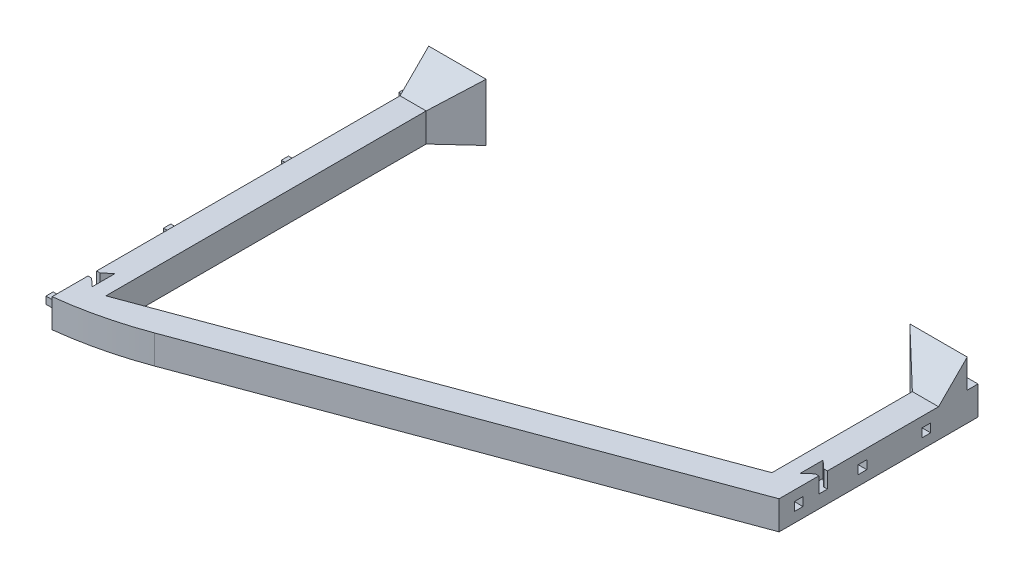
SolidWorks part; units mm, degrees
ref_plane "Přední rovina" through (0, 0, 0) normal (0, 0, 1) x (1, 0, 0)
ref_plane "Horní rovina" through (0, 0, 0) normal (0, 1, 0) x (1, 0, 0)
ref_plane "Pravá rovina" through (0, 0, 0) normal (1, 0, 0) x (0, 0, -1)
sketch "Skica1" plane through (0, 0, 0) normal (0, 1, 0) x (1, 0, 0)
  line L0 (0, 0) -> (0, -111)
  line L1 (0, -111) -> (150.15, -55.45)
  line L2 (150.15, -55.45) -> (150.15, 0)
  line L3 (150.15, 0) -> (142.85, 0)
  line L4 (142.85, 0) -> (142.85, -50.1539)
  line L5 (142.85, -50.1539) -> (7.3, -100.3024)
  line L6 (7.3, -100.3024) -> (7.3, 0)
  line L7 (7.3, 0) -> (0, 0)
  dimension "D1" = 7.3
  dimension "D2" = 7.3
  dimension "D3" = 111
  dimension "D4" = 7.5
  dimension "D5" = 150.15
  dimension "D6" = 55.45
extrude "Přidat vysunutím1" add sketch "Skica1" along normal blind 8
sketch "Skica2" plane through (0, 8, 0) normal (0, 1, 0) x (1, 0, 0)
  line L5 (0, -95.6) -> (1, -95.6)
  line L6 (0, 0) -> (0, -111) construction
  line L7 (1, -95.6) -> (3.2, -93.6)
  line L8 (3.2, -93.6) -> (3.2, -100)
  line L9 (3.2, -100) -> (1, -98)
  line L10 (1, -98) -> (0, -98)
  line L11 (0, -98) -> (0, -95.6)
  dimension "D1" = 6.4
  dimension "D2" = 2.4
  dimension "D3" = 1
  dimension "D4" = 1
  dimension "D5" = 2
  dimension "D6" = 3.2
  dimension "D7" = 11
extrude "Odebrat vysunutím1" cut sketch "Skica2" against normal blind 4.4
sketch "Skica3" plane through (0, 0, 0) normal (-1, 0, 0) x (0, 0, 1)
  line L0 (0, 8) -> (0, 0) construction
  line L1 (5.3, 5) -> (7.3, 5)
  line L2 (5.3, 5) -> (5.3, 3)
  line L3 (5.3, 3) -> (7.3, 3)
  line L4 (7.3, 5) -> (7.3, 3)
  line L5 (38.1, 5) -> (40.1, 5)
  line L6 (38.1, 5) -> (38.1, 3)
  line L7 (38.1, 3) -> (40.1, 3)
  line L8 (40.1, 5) -> (40.1, 3)
  line L9 (70.9, 5) -> (72.9, 5)
  line L10 (70.9, 5) -> (70.9, 3)
  line L11 (70.9, 3) -> (72.9, 3)
  line L12 (72.9, 5) -> (72.9, 3)
  line L17 (0, 8) -> (95.6, 8) construction
  line L18 (98, 8) -> (111, 8) construction
  line L19 (103.7, 5) -> (105.7, 5)
  line L20 (103.7, 5) -> (103.7, 3)
  line L21 (103.7, 3) -> (105.7, 3)
  line L22 (105.7, 5) -> (105.7, 3)
  point P16 (5.3, 4)
  dimension "D1" = 5.3
  dimension "D2" = 2
  dimension "D3" = 2
  dimension "D4" = 3
  dimension "D5" = 2
  dimension "D6" = 2
  dimension "D7" = 3
  dimension "D8" = 30.8
  dimension "D9" = 2
  dimension "D10" = 2
  dimension "D11" = 3
  dimension "D12" = 30.8
  dimension "D13" = 2
  dimension "D14" = 2
  dimension "D15" = 3
  dimension "D16" = 30.8
extrude "Přidat vysunutím2" add sketch "Skica3" along normal blind 4
sketch "Skica5" plane through (0, 8, 0) normal (0, 1, 0) x (1, 0, 0)
  line L0 (0, 0) -> (0, -95.6) construction
  line L1 (0, -3) -> (16, -3)
  line L2 (0, -3) -> (0, -11)
  line L3 (0, -11) -> (16, -11)
  line L4 (16, -3) -> (16, -11)
  line L5 (150.15, -55.45) -> (150.15, 0) construction
  line L6 (150.15, -3) -> (134.15, -3)
  line L7 (150.15, -3) -> (150.15, -11)
  line L8 (150.15, -11) -> (134.15, -11)
  line L9 (134.15, -3) -> (134.15, -11)
  line L10 (150.15, 0) -> (142.85, 0) construction
  line L11 (7.3, 0) -> (0, 0) construction
  dimension "D1" = 8
  dimension "D2" = 8
  dimension "D3" = 16
  dimension "D4" = 16
  dimension "D5" = 3
  dimension "D6" = 3
extrude "Přidat vysunutím3" add sketch "Skica5" against normal blind 16 from offset 8
sketch "Skica6" plane through (150.15, 0, 0) normal (1, 0, 0) x (0, 0, -1)
  line L0 (-11, 8) -> (-11, 16)
  line L1 (-11, 16) -> (-3, 16)
  line L2 (-3, 16) -> (-11, 8)
extrude "Odebrat vysunutím3" cut sketch "Skica6" against normal through all
sketch "Skica7" plane through (0, 0, 0) normal (0, -1, 0) x (1, 0, 0)
  line L0 (7.3, 11) -> (16, 3)
  line L1 (16, 3) -> (16, 11)
  line L2 (16, 11) -> (7.3, 11)
  line L3 (134.15, 3) -> (134.15, 11)
  line L4 (134.15, 11) -> (142.85, 11)
  line L5 (142.85, 11) -> (134.15, 3)
extrude "Odebrat vysunutím4" cut sketch "Skica7" against normal through all
sketch "Skica4" plane through (150.15, 0, 0) normal (1, 0, 0) x (0, 0, -1)
  line L0 (-55.45, 8) -> (-11, 8) construction
  line L1 (-51.2, 5.2) -> (-48.8, 5.2)
  line L2 (-51.2, 5.2) -> (-51.2, 2.8)
  line L3 (-51.2, 2.8) -> (-48.8, 2.8)
  line L4 (-48.8, 5.2) -> (-48.8, 2.8)
  line L5 (-33.4, 5.2) -> (-31, 5.2)
  line L6 (-33.4, 5.2) -> (-33.4, 2.8)
  line L7 (-33.4, 2.8) -> (-31, 2.8)
  line L8 (-31, 5.2) -> (-31, 2.8)
  line L9 (-15.6, 5.2) -> (-13.2, 5.2)
  line L10 (-15.6, 5.2) -> (-15.6, 2.8)
  line L11 (-15.6, 2.8) -> (-13.2, 2.8)
  line L12 (-13.2, 5.2) -> (-13.2, 2.8)
  line L14 (0, 8) -> (0, 0) construction
  point P16 (-31, 4)
  dimension "D1" = 2.4
  dimension "D2" = 2.4
  dimension "D3" = 2.8
  dimension "D4" = 2.4
  dimension "D5" = 2.4
  dimension "D6" = 2.8
  dimension "D7" = 2.4
  dimension "D8" = 2.4
  dimension "D9" = 2.8
  dimension "D10" = 13.2
  dimension "D11" = 15.4
  dimension "D12" = 15.4
extrude "Odebrat vysunutím2" cut sketch "Skica4" against normal blind 4.4
sketch "Skica8" plane through (0, 8, 0) normal (0, 1, 0) x (1, 0, 0)
  line L6 (150.15, -42) -> (149.15, -42)
  line L7 (150.15, -55.45) -> (150.15, -11) construction
  line L8 (149.15, -42) -> (146.95, -40)
  line L9 (146.95, -40) -> (146.95, -46.4)
  line L10 (146.95, -46.4) -> (149.15, -44.4)
  line L11 (150.15, -44.4) -> (150.15, -42)
  line L12 (149.15, -44.4) -> (150.15, -44.4)
  line L13 (150.15, 0) -> (142.85, 0) construction
  point P10 (146.5, 0)
  dimension "D1" = 6.4
  dimension "D2" = 1
  dimension "D3" = 2.4
  dimension "D4" = 2
  dimension "D5" = 3.2
  dimension "D6" = 40
  dimension "D7" = 1
extrude "Odebrat vysunutím5" cut sketch "Skica8" against normal blind 4.4
sketch "Skica9" plane through (0, 8, 0) normal (0, 1, 0) x (1, 0, 0)
  line L0 (0, -108) -> (8.1089, -108)
  line L1 (0, -98) -> (0, -111) construction
  line L2 (0, -111) -> (150.15, -55.45) construction
  line L3 (8.1089, -108) -> (0, -111)
  line L4 (0, -111) -> (0, -108)
  dimension "D1" = 3
extrude "Odebrat vysunutím6" cut sketch "Skica9" against normal through all
fillet "Zaoblit1" radius 100 1 edges at (8.1089, 4, 108)
